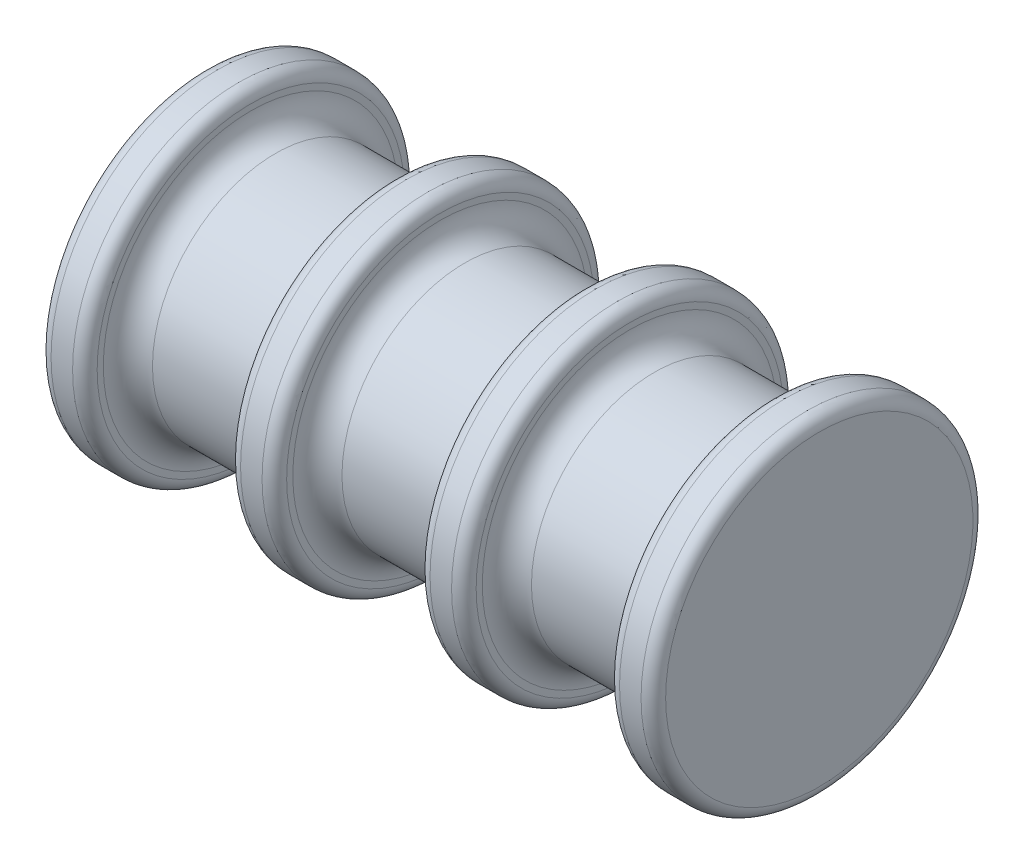
SolidWorks part; units mm, degrees
ref_plane "Front Plane" through (0, 0, 0) normal (0, 0, 1) x (1, 0, 0)
ref_plane "Top Plane" through (0, 0, 0) normal (0, 1, 0) x (1, 0, 0)
ref_plane "Right Plane" through (0, 0, 0) normal (1, 0, 0) x (0, 0, -1)
sketch "Sketch1" plane through (0, 0, 0) normal (0, 1, 0) x (1, 0, 0)
  line L0 (0, 0) -> (97.119, 0) construction
  line L1 (0.762, 10.287) -> (2.0955, 10.287)
  line L2 (2.8575, 9.525) -> (2.8575, 9.144)
  line L3 (4.3815, 7.62) -> (10.2235, 7.62)
  line L4 (11.7475, 9.144) -> (11.7475, 9.525)
  line L5 (12.5095, 10.287) -> (13.843, 10.287)
  line L6 (14.605, 9.525) -> (14.605, 9.144)
  line L7 (16.129, 7.62) -> (21.971, 7.62)
  line L8 (23.495, 9.144) -> (23.495, 9.525)
  line L9 (24.257, 10.287) -> (25.5905, 10.287)
  line L10 (26.3525, 9.525) -> (26.3525, 9.144)
  line L11 (27.8765, 7.62) -> (33.7185, 7.62)
  line L12 (35.2425, 9.144) -> (35.2425, 9.525)
  line L13 (36.0045, 10.287) -> (37.338, 10.287)
  line L14 (38.1, 9.525) -> (38.1, 0)
  line L15 (38.1, 0) -> (0, 0)
  line L16 (0, 0) -> (0, 9.525)
  arc A0 (37.338, 10.287) -> (38.1, 9.525) centre (37.338, 9.525) cw
  arc A1 (35.2425, 9.525) -> (36.0045, 10.287) centre (36.0045, 9.525) cw
  arc A2 (25.5905, 10.287) -> (26.3525, 9.525) centre (25.5905, 9.525) cw
  arc A3 (23.495, 9.525) -> (24.257, 10.287) centre (24.257, 9.525) cw
  arc A4 (13.843, 10.287) -> (14.605, 9.525) centre (13.843, 9.525) cw
  arc A5 (11.7475, 9.525) -> (12.5095, 10.287) centre (12.5095, 9.525) cw
  arc A6 (0.762, 10.287) -> (0, 9.525) centre (0.762, 9.525) ccw
  arc A7 (2.0955, 10.287) -> (2.8575, 9.525) centre (2.0955, 9.525) cw
  arc A8 (33.7185, 7.62) -> (35.2425, 9.144) centre (33.7185, 9.144) ccw
  arc A9 (26.3525, 9.144) -> (27.8765, 7.62) centre (27.8765, 9.144) ccw
  arc A10 (21.971, 7.62) -> (23.495, 9.144) centre (21.971, 9.144) ccw
  arc A11 (14.605, 9.144) -> (16.129, 7.62) centre (16.129, 9.144) ccw
  arc A12 (10.2235, 7.62) -> (11.7475, 9.144) centre (10.2235, 9.144) ccw
  arc A13 (2.8575, 9.144) -> (4.3815, 7.62) centre (4.3815, 9.144) ccw
  point P44 (11.7475, 7.62)
  point P47 (2.8575, 7.62)
  dimension "D3" = 0.762
  dimension "D4" = 1.524
  dimension "D1" = 38.1
  dimension "D2" = 8.89
  dimension "D5" = 9.525
  dimension "D6" = 7.62
  dimension "D7" = 7.62
  dimension "D8" = 7.62
revolve "Revolve1" add sketch "Sketch1" angle 360 about L0
sketch "Sketch3" plane through (0, 0, 0) normal (-1, 0, 0) x (0, 0, 1)
  circle A0 centre (0, 0) radius 5.08
  circle A1 centre (0, 0) radius 3.81
  dimension "D1" = 10.16
extrude "Cut-Extrude1" cut sketch "Sketch3" against normal blind 0.254
sketch "Sketch4" plane through (0, 0, 0) normal (-1, 0, 0) x (0, 0, 1)
  circle A0 centre (0, 0) radius 1.2659
  circle A1 centre (0, 0) radius 1.789
extrude "Cut-Extrude2" cut sketch "Sketch4" against normal blind 0.2032
fillet "Fillet1" radius 0.0254 2 edges at (0, 0, 5.08) (0.254, 0, 5.08)
fillet "Fillet3" radius 0.1016 3 edges at (0, 0, 1.2659) (0.2032, 0, 1.789) (0, 0, 1.789)
fillet "Fillet5" radius 0.127 2 edges at (0.254, 0, 3.81) (0, 0, 3.81)
